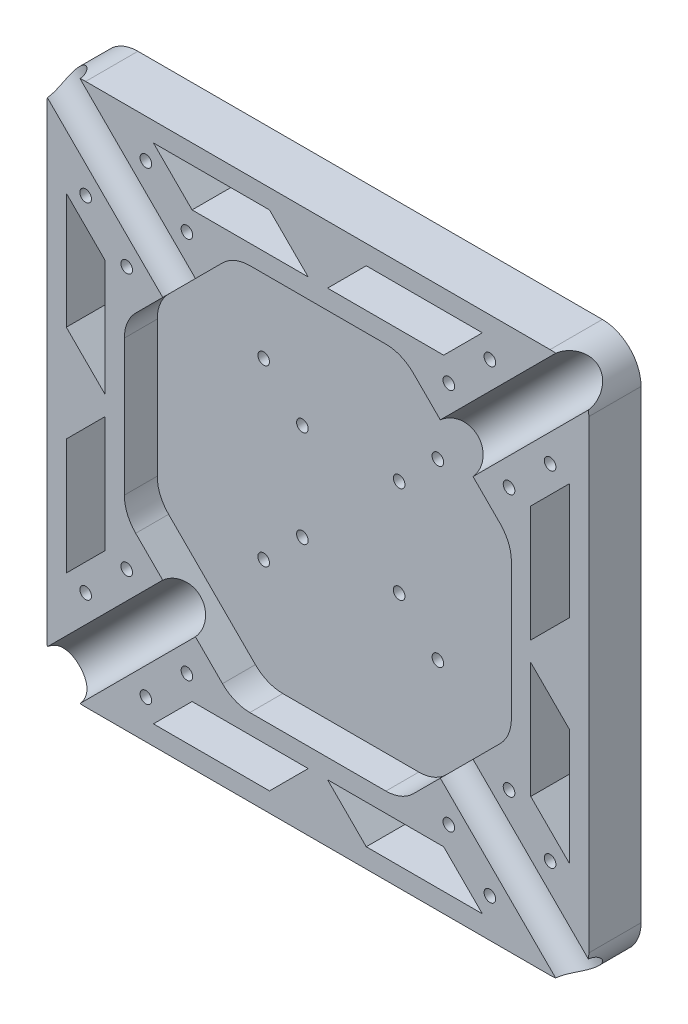
SolidWorks part; units mm, degrees
ref_plane "Plan de face" through (0, 0, 0) normal (0, 0, 1) x (1, 0, 0)
ref_plane "Plan de dessus" through (0, 0, 0) normal (0, 1, 0) x (1, 0, 0)
ref_plane "Plan de droite" through (0, 0, 0) normal (1, 0, 0) x (0, 0, -1)
sketch "Esquisse1" plane through (0, 0, 0) normal (0, 0, 1) x (1, 0, 0)
  line L0 (55, 75.9996) -> (55, -81.4607) construction
  line L1 (-70, 70) -> (70, 70)
  line L2 (-70, 70) -> (-70, -70)
  line L3 (-70, -70) -> (70, -70)
  line L4 (70, 70) -> (70, -70)
  line L9 (65, 75.9996) -> (65, -81.4607) construction
  line L10 (50, 0) -> (70, 0) construction
  line L11 (52.5, 0) -> (65, 12.5) construction
  line L12 (65, 12.5) -> (55, 2.5)
  line L13 (65, -12.5) -> (52.5, 0) construction
  line L14 (65, -12.5) -> (55, -2.5)
  line L15 (65, -12.5) -> (65, -42.5)
  line L16 (65, -42.5) -> (55, -32.5)
  line L17 (55, -32.5) -> (55, -2.5)
  line L18 (65, 12.5) -> (65, 42.5)
  line L19 (65, 42.5) -> (55, 32.5)
  line L20 (55, 32.5) -> (55, 2.5)
  line L21 (12.5, -65) -> (2.5, -55)
  line L22 (-12.5, -65) -> (-2.5, -55)
  line L23 (-12.5, -65) -> (-42.5, -65)
  line L24 (-42.5, -65) -> (-32.5, -55)
  line L25 (-32.5, -55) -> (-2.5, -55)
  line L26 (12.5, -65) -> (42.5, -65)
  line L27 (42.5, -65) -> (32.5, -55)
  line L28 (32.5, -55) -> (2.5, -55)
  line L29 (0, -52.5) -> (12.5, -65) construction
  line L30 (-12.5, -65) -> (0, -52.5) construction
  line L31 (-65, -12.5) -> (-55, -2.5)
  line L32 (-65, 12.5) -> (-55, 2.5)
  line L33 (-65, 12.5) -> (-65, 42.5)
  line L34 (-65, 42.5) -> (-55, 32.5)
  line L35 (-55, 32.5) -> (-55, 2.5)
  line L36 (-65, -12.5) -> (-65, -42.5)
  line L37 (-65, -42.5) -> (-55, -32.5)
  line L38 (-55, -32.5) -> (-55, -2.5)
  line L39 (-52.5, 0) -> (-65, -12.5) construction
  line L40 (-65, 12.5) -> (-52.5, 0) construction
  line L41 (-12.5, 65) -> (-2.5, 55)
  line L42 (12.5, 65) -> (2.5, 55)
  line L43 (12.5, 65) -> (42.5, 65)
  line L44 (42.5, 65) -> (32.5, 55)
  line L45 (32.5, 55) -> (2.5, 55)
  line L46 (-12.5, 65) -> (-42.5, 65)
  line L47 (-42.5, 65) -> (-32.5, 55)
  line L48 (-32.5, 55) -> (-2.5, 55)
  line L49 (0, 52.5) -> (-12.5, 65) construction
  line L50 (12.5, 65) -> (0, 52.5) construction
  dimension "D1" = 140
  dimension "D2" = 140
  dimension "D3" = 70
  dimension "D4" = 70
  dimension "D10" = 5
  dimension "D11" = 2.5
  dimension "D12" = 12.5
  dimension "D13" = 30
  dimension "D14" = 30
  dimension "D15" = 30
  dimension "D16" = 30
  dimension "D17" = 4
extrude "Boss.-Extru.1" add sketch "Esquisse1" along normal blind 13.5
ref_plane "Plan1" through (0, 0, 0) normal (-0.7071, 0.7071, 0) x (-0.7071, -0.7071, 0)
sketch "Esquisse4" plane through (0, 0, 13.5) normal (0, 0, 1) x (1, 0, 0)
  line L0 (-21.7157, 50) -> (-50, 21.7157)
  line L1 (-50, 50) -> (50, 50) construction
  line L2 (-50, 50) -> (-50, -50) construction
  line L3 (-50, -50) -> (50, -50) construction
  line L4 (50, 50) -> (50, -50) construction
  line L5 (-50, -21.7157) -> (-21.7157, -50)
  line L6 (21.7157, -50) -> (50, -21.7157)
  line L7 (21.7157, 50) -> (50, 21.7157)
  line L8 (-50, 21.7157) -> (-50, -21.7157)
  line L9 (-21.7157, -50) -> (21.7157, -50)
  line L10 (50, -21.7157) -> (50, 21.7157)
  line L11 (21.7157, 50) -> (-21.7157, 50)
  dimension "D1" = 100
  dimension "D2" = 100
  dimension "D3" = 50
  dimension "D4" = 50
  dimension "D5" = 20
  dimension "D6" = 20
  dimension "D7" = 20
  dimension "D8" = 20
extrude "Enlèv. mat.-Extru.3" cut sketch "Esquisse4" against normal blind 8.5
sketch "Esquisse2" plane through (0, 0, 0) normal (-0.7071, 0.7071, 0) x (-0.7071, -0.7071, 0)
  line L0 (99.7696, 14) -> (-97.6372, 14) construction
  line L1 (-6, 14) -> (6, 14)
  arc A0 (-6, 14) -> (6, 14) centre (0, 14) ccw
  dimension "D1" = 14
extrude "Enlèv. mat.-Extru.1" cut sketch "Esquisse2" against normal blind 100 and the other way blind 100
ref_axis "Axe1" through (0, 0, -62.842) along (0, 0, 1)
pattern_circular "Répétition circulaire1" count 2 every 90 about axis through (0, 0, -62.842) along (0, 0, 1) of "Enlèv. mat.-Extru.1"
fillet "Congé1" radius 10 12 edges at (-70, 70, 4) (-70, -70, 4) (70, 70, 4) (70, -70, 4) (-21.7157, -50, 9.25) (21.7157, -50, 9.25) (50, -21.7157, 9.25) (50, 21.7157, 9.25) (21.7157, 50, 9.25) (-21.7157, 50, 9.25) (-50, -21.7157, 9.25) (-50, 21.7157, 9.25)
sketch "Esquisse3" plane through (0, 0, 13.5) normal (0, 0, 1) x (1, 0, 0)
  line L0 (-60, -70) -> (60, -70) construction
  line L1 (-70, 60) -> (-70, -60) construction
  line L2 (45.3482, 45.3482) -> (-45.3482, -45.3482) construction
  circle A0 centre (-60, -44.4437) radius 1.5
  circle A1 centre (-44.4437, -60) radius 1.5
  circle A2 centre (-44.4437, 60) radius 1.5
  circle A3 centre (-60, 44.4437) radius 1.5
  circle A4 centre (60, 44.4437) radius 1.5
  circle A5 centre (44.4437, 60) radius 1.5
  circle A6 centre (44.4437, -60) radius 1.5
  circle A7 centre (60, -44.4437) radius 1.5
  dimension "D1" = 3
  dimension "D2" = 3
  dimension "D3" = 10
  dimension "D4" = 10
  dimension "D5" = 11
  dimension "D6" = 11
  dimension "D7" = 4
extrude "Enlèv. mat.-Extru.2" cut sketch "Esquisse3" against normal blind 13.5
sketch "Esquisse5" plane through (0, 0, 5) normal (0, 0, 1) x (1, 0, 0)
  line L0 (-70, 60) -> (-70, -60) construction
  line L1 (60, 70) -> (-60, 70) construction
  line L2 (45.3482, 45.3482) -> (-45.3482, -45.3482) construction
  circle A0 centre (-22.5, 22.5) radius 1.5
  circle A1 centre (22.5, 22.4985) radius 1.5
  circle A2 centre (-22.5, -22.5) radius 1.5
  circle A3 centre (22.5, -22.5015) radius 1.5
  circle A4 centre (-12.5, 12.5) radius 1.5
  circle A5 centre (12.5, 12.5) radius 1.5
  circle A6 centre (12.5, -12.5) radius 1.5
  circle A7 centre (-12.5, -12.5) radius 1.5
  circle A8 centre (33.837, 49.3934) radius 1.5
  circle A9 centre (49.3934, 33.837) radius 1.5
  circle A10 centre (49.3934, -33.837) radius 1.5
  circle A11 centre (33.837, -49.3934) radius 1.5
  circle A12 centre (-33.837, -49.3934) radius 1.5
  circle A13 centre (-49.3934, -33.837) radius 1.5
  circle A14 centre (-49.3934, 33.837) radius 1.5
  circle A15 centre (-33.837, 49.3934) radius 1.5
  circle A16 centre (60, 44.4437) radius 1.5 construction
  circle A17 centre (44.4437, 60) radius 1.5 construction
  dimension "D1" = 3
  dimension "D2" = 3
  dimension "D3" = 3
  dimension "D4" = 3
  dimension "D12" = 3
  dimension "D21" = 3
  dimension "D22" = 3
  dimension "D16" = 15
  dimension "D17" = 11
  dimension "D18" = 15
  dimension "D5" = 45
  dimension "D6" = 45
  dimension "D7" = 45
  dimension "D8" = 45
  dimension "D9" = 22.5
  dimension "D10" = 22.5
  dimension "D11" = 57.5
  dimension "D13" = 57.5
  dimension "D15" = 11
  dimension "D14" = 4
  dimension "D24" = 4
extrude "Enlèv. mat.-Extru.4" cut sketch "Esquisse5" against normal blind 12.5 and the other way blind 10
